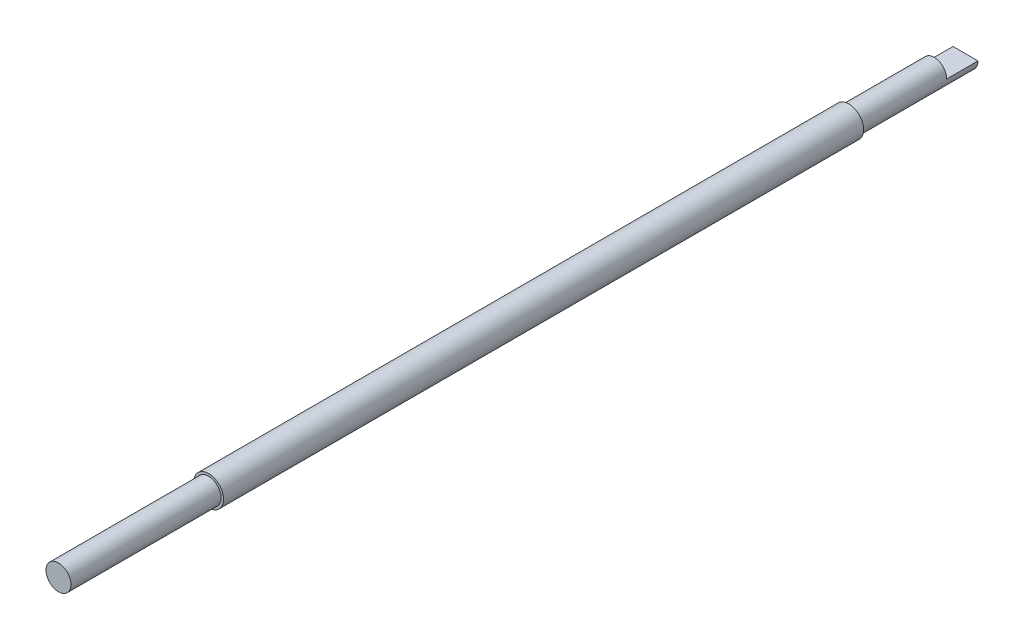
SolidWorks part; units mm, degrees
ref_plane "Front Plane" through (0, 0, 0) normal (0, 0, 1) x (1, 0, 0)
ref_plane "Top Plane" through (0, 0, 0) normal (0, 1, 0) x (1, 0, 0)
ref_plane "Right Plane" through (0, 0, 0) normal (1, 0, 0) x (0, 0, -1)
sketch "Sketch1" plane through (0, 0, 0) normal (0, 0, 1) x (1, 0, 0)
  circle A0 centre (0, 0) radius 4.7625
  dimension "D1" = 9.525
extrude "Boss-Extrude1" add sketch "Sketch1" along normal blind 290
sketch "Sketch3" plane through (0, 0, 0) normal (0, 0, -1) x (-1, 0, 0)
  circle A0 centre (0, 0) radius 4.7625
  circle A1 centre (0, 0) radius 4
  dimension "D1" = 9.525
  dimension "D2" = 8
extrude "Cut-Extrude2" cut sketch "Sketch3" against normal blind 37.32
sketch "Sketch4" plane through (0, 0, 0) normal (0, 0, -1) x (-1, 0, 0)
  line L0 (-4, 0) -> (4, 0)
  circle A0 centre (0, 0) radius 4 construction
  circle A1 centre (0, 0) radius 4 construction
  circle A2 centre (0, 0) radius 4
  circle M2 centre (0, 0) radius 4
  dimension "D1" = 8
  dimension "D2" = 8
extrude "Cut-Extrude3" cut sketch "Sketch4" against normal blind 10 contours L0 M2 region at (0, 1.6977, 0)
sketch "Sketch5" plane through (0, 0, 290) normal (0, 0, 1) x (1, 0, 0)
  circle A0 centre (0, 0) radius 4
  circle A1 centre (0, 0) radius 4.7625
  dimension "D1" = 8
  dimension "D2" = 9.525
extrude "Cut-Extrude4" cut sketch "Sketch5" against normal blind 48
